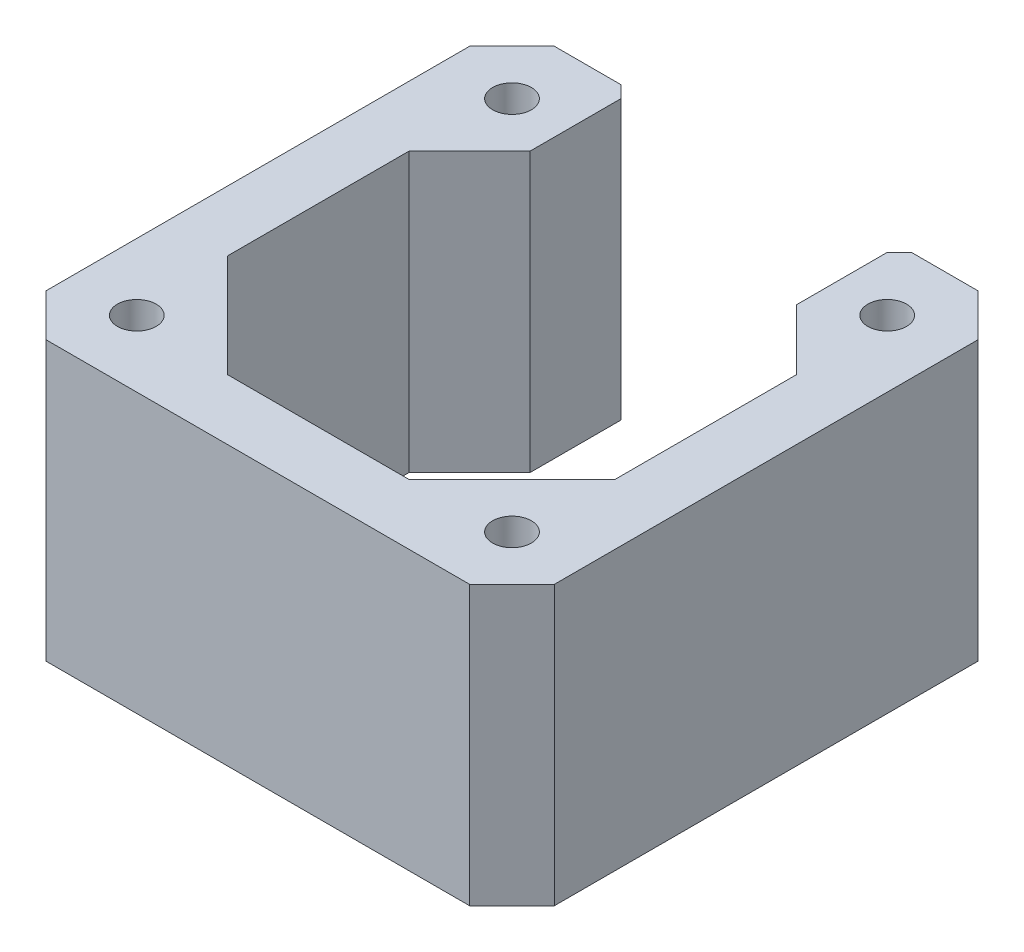
SolidWorks part; units mm, degrees
material "PET-G"
ref_plane "Спереди" through (0, 0, 0) normal (0, 0, 1) x (1, 0, 0)
ref_plane "Сверху" through (0, 0, 0) normal (0, 1, 0) x (1, 0, 0)
ref_plane "Справа" through (0, 0, 0) normal (1, 0, 0) x (0, 0, -1)
sketch "Sketch1" plane through (0, 0, 0) normal (0, 1, 0) x (1, 0, 0)
  line L0 (-16, -7.5) -> (-7.5, -16)
  line L1 (-7.5, -16) -> (7.5, -16)
  line L2 (-17.5, 21) -> (-21, 17.5)
  line L3 (-21, 17.5) -> (-21, -17.5)
  line L4 (-21, -17.5) -> (-17.5, -21)
  line L5 (-17.5, -21) -> (17.5, -21)
  line L6 (21, -17.5) -> (17.5, -21)
  line L7 (16, -7.5) -> (7.5, -16)
  line L8 (16, 7.5) -> (16, -7.5)
  line L9 (-17.5, 21) -> (-12, 21)
  line L10 (-16, 7.5) -> (-16, -7.5)
  line L11 (0, 0) -> (0, 30.1714) construction
  line L12 (-11, 20) -> (-11, 12.5)
  line L13 (-11, 12.5) -> (-16, 7.5)
  line L14 (21, 17.5) -> (21, -17.5)
  line L15 (17.5, 21) -> (21, 17.5)
  line L16 (17.5, 21) -> (12, 21)
  line L17 (11, 20) -> (11, 12.5)
  line L18 (11, 12.5) -> (16, 7.5)
  line L19 (-12, 21) -> (-11, 20)
  line L20 (12, 21) -> (11, 20)
  circle A0 centre (-15.5, 15.5) radius 1.6
  circle A1 centre (-15.5, -15.5) radius 1.6
  circle A2 centre (15.5, -15.5) radius 1.6
  circle A3 centre (15.5, 15.5) radius 1.6
  point P0 (-11, 21)
  point P1 (0, 0)
  point P7 (15.5, -14.784)
  point P8 (0, 0)
  point P9 (-90.6575, 29.3473)
  point P37 (11, 21)
  dimension "D13" = 3.2
  dimension "D20" = 3.2
  dimension "D3" = 22
  dimension "D4" = 5
  dimension "D5" = 3.5
  dimension "D6" = 42
  dimension "D7" = 16
  dimension "D10" = 3.5
  dimension "D11" = 3.5
  dimension "D12" = 5
  dimension "D14" = 31
  dimension "D15" = 15.5
  dimension "D16" = 15
  dimension "D17" = 7.5
  dimension "D18" = 31
  dimension "D21" = 42
extrude "Base" add sketch "Sketch1" along normal blind 23 and the other way blind 0.0001
